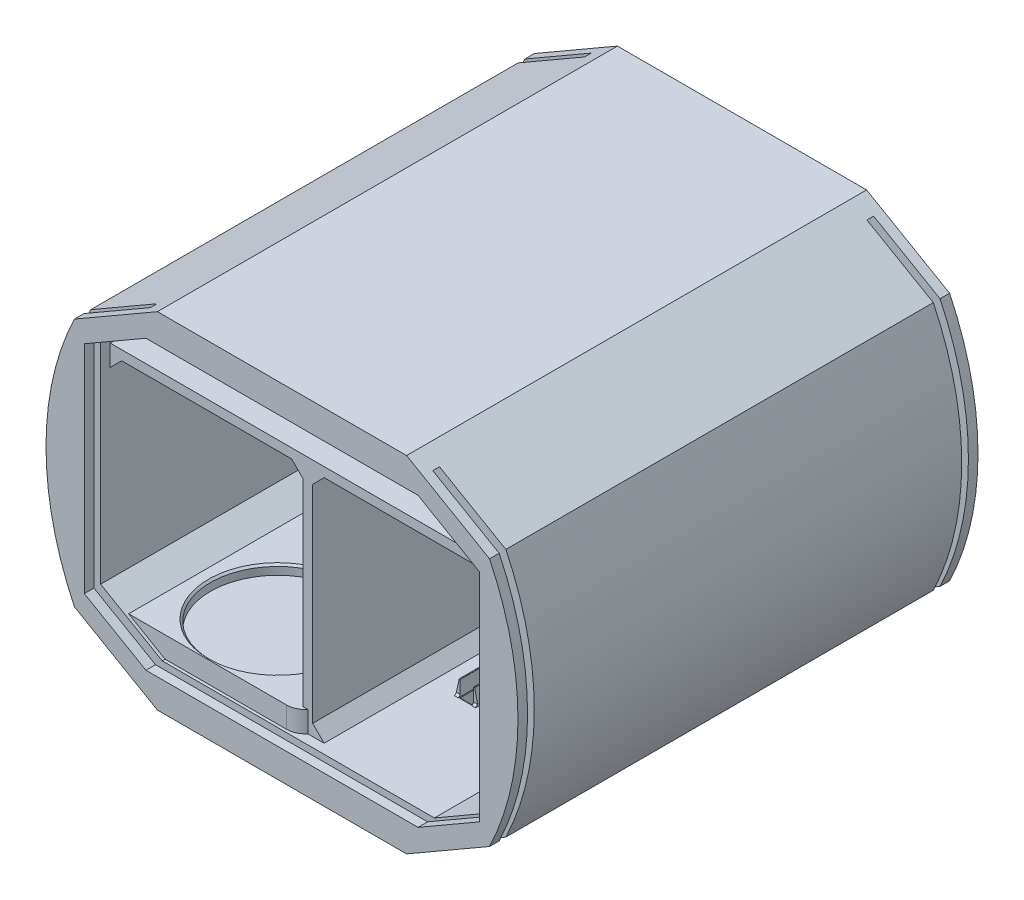
SolidWorks part; units mm, degrees
ref_plane "Front Plane" through (0, 0, 0) normal (0, 0, 1) x (1, 0, 0)
ref_plane "Top Plane" through (0, 0, 0) normal (0, 1, 0) x (1, 0, 0)
ref_plane "Right Plane" through (0, 0, 0) normal (1, 0, 0) x (0, 0, -1)
sketch "Sketch1" plane through (0, 0, 0) normal (0, 0, 1) x (1, 0, 0)
  line L0 (-65, 90) -> (-108.3013, 65)
  line L1 (-65, -90) -> (65, -90)
  line L3 (-65, 90) -> (65, 90)
  line L5 (-65, -90) -> (65, 90) construction
  line L6 (-65, 90) -> (65, -90) construction
  line L7 (-65, -90) -> (-108.3013, -65)
  line L8 (65, 90) -> (108.3013, 65)
  line L9 (65, -90) -> (108.3013, -65)
  arc A1 (-108.3013, 65) -> (-108.3013, -65) centre (26.8838, 0) ccw
  arc A4 (108.3013, 65) -> (108.3013, -65) centre (-26.8838, 0) cw
  point P0 (0, 0)
  point P7 (0, -90)
  dimension "D13" = 150
  dimension "D14" = 150
  dimension "D1" = 180
  dimension "D2" = 130
  dimension "D3" = 130
  dimension "D4" = 0
  dimension "D5" = 50
  dimension "D6" = 150
  dimension "D7" = 50
  dimension "D8" = 150
  dimension "D9" = 50
  dimension "D10" = 150
  dimension "D11" = 50
  dimension "D12" = 150
extrude "Boss-Extrude1" add sketch "Sketch1" along normal blind 240
sketch "Sketch2" plane through (0, 0, 240) normal (0, 0, 1) x (1, 0, 0)
  line L0 (-70.9808, 75) -> (70.9808, 75)
  line L1 (70.9808, 75) -> (103.1162, 56.4466)
  line L3 (65, 90) -> (-65, 90) construction
  line L4 (-70.9808, -75) -> (70.9808, -75)
  line L5 (70.9808, -75) -> (103.1162, -56.4466)
  line L6 (-65, -90) -> (65, -90) construction
  line L7 (108.3013, 65) -> (65, 90) construction
  line L8 (65, -90) -> (108.3013, -65) construction
  line L9 (-70.9808, 75) -> (-103.1162, 56.4466)
  line L10 (-70.9808, -75) -> (-103.1162, -56.4466)
  line L13 (-65, 90) -> (-108.3013, 65) construction
  line L15 (-108.3013, -65) -> (-65, -90) construction
  line L16 (-103.1162, 56.4466) -> (-103.1162, -56.4466)
  line L17 (103.1162, 56.4466) -> (103.1162, -56.4466)
  arc A0 (-108.3013, 65) -> (-108.3013, -65) centre (26.8838, 0) ccw construction
  arc A1 (108.3013, -65) -> (108.3013, 65) centre (-26.8838, 0) ccw construction
  point P24 (-123.1162, 0)
  point P28 (123.1162, 0)
  dimension "D1" = 15
  dimension "D2" = 10
  dimension "D3" = 20
  dimension "D4" = 15
  dimension "D5" = 20
  dimension "D7" = 10
  dimension "D8" = 10
  dimension "D10" = 10
sketch "Sketch3" plane through (0, 0, 0) normal (1, 0, 0) x (0, 0, -1)
  line L0 (-240, 90) -> (0, 90) construction
  line L1 (-235, 85) -> (-231.5, 85)
  line L2 (-235, 85) -> (-235, -85)
  line L3 (-235, -85) -> (-231.5, -85)
  line L4 (-231.5, 85) -> (-231.5, -85)
  line L5 (-240, -90) -> (0, -90) construction
  line L6 (-240, 65) -> (-240, -65) construction
  line L8 (-8.5, 85) -> (-5, 85)
  line L9 (-8.5, 85) -> (-8.5, -85)
  line L10 (-8.5, -85) -> (-5, -85)
  line L11 (-5, 85) -> (-5, -85)
  line L12 (0, -65) -> (0, 65) construction
  dimension "D1" = 5
  dimension "D2" = 5
  dimension "D3" = 5
  dimension "D4" = 3.5
  dimension "D5" = 5
  dimension "D6" = 5
  dimension "D7" = 5
  dimension "D8" = 3.5
extrude "Cut-Extrude4" cut sketch "Sketch2" against normal through all both and the other way through all
extrude "Cut-Extrude5" cut sketch "Sketch3" against normal through all both and the other way through all
sketch "Sketch7" plane through (0, 0, 0) normal (1, 0, 0) x (0, 0, -1)
  line L0 (-231.5, 65) -> (-231.5, -65) construction
  line L1 (-226.5, 45) -> (-13.5, 45)
  line L2 (-226.5, 45) -> (-226.5, 50)
  line L3 (-226.5, 50) -> (-13.5, 50)
  line L4 (-13.5, 45) -> (-13.5, 50)
  line L5 (-226.5, 45) -> (-13.5, 50) construction
  line L6 (-226.5, 50) -> (-13.5, 45) construction
  line L7 (-8.5, -65) -> (-8.5, 65) construction
  line L8 (-8.5, 75) -> (-231.5, 75) construction
  point P0 (-120, 47.5)
  dimension "D1" = 5
  dimension "D2" = 5
  dimension "D3" = 5
  dimension "D4" = 25
extrude "Boss-Extrude4" add sketch "Sketch7" along normal up to surface and the other way up to surface up to face at (103.1162, 0, 120) other way up to face at (-103.1162, 0, 120)
chamfer "Chamfer7" distance 6 angle 45 2 edges at (103.1162, 45, 120) (-103.1162, 45, 120)
sketch "Sketch8" plane through (0, -75, 0) normal (0, 1, 0) x (1, 0, 0)
  line L0 (-73.6603, -8.5) -> (-108.3013, -8.5) construction
  line L1 (-2.5, -226.5) -> (2.5, -226.5)
  line L2 (-2.5, -226.5) -> (-2.5, -13.5)
  line L3 (-2.5, -13.5) -> (2.5, -13.5)
  line L4 (2.5, -226.5) -> (2.5, -13.5)
  line L5 (-2.5, -226.5) -> (2.5, -13.5) construction
  line L6 (-2.5, -13.5) -> (2.5, -226.5) construction
  line L7 (-108.3013, -231.5) -> (-73.6603, -231.5) construction
  point P0 (0, -120)
  dimension "D1" = 5
  dimension "D2" = 5
  dimension "D3" = 5
extrude "Boss-Extrude5" add sketch "Sketch8" along normal up to surface (120 mm away) up to face at (0, 45, 120)
chamfer "Chamfer8" distance 6 angle 45 4 edges at (-2.5, 45, 120) (2.5, 45, 120) (2.5, -75, 120) (-2.5, -75, 120)
sketch "Sketch10" plane through (0, 0, 0) normal (1, 0, 0) x (0, 0, -1)
  line L0 (-240, -90) -> (0, -90) construction
  line L1 (-132.5, -75) -> (-107.5, -75)
  line L2 (-132.5, -75) -> (-132.5, -69)
  line L3 (-132.5, -69) -> (-107.5, -69)
  line L4 (-107.5, -75) -> (-107.5, -69)
  line L5 (-132.5, -75) -> (-107.5, -69) construction
  line L6 (-132.5, -69) -> (-107.5, -75) construction
  line L7 (-13.5, -75) -> (-226.5, -75) construction
  line L8 (-226.5, -69) -> (-13.5, -69) construction
  point P0 (-120, -72)
  point P7 (-120, -90)
  point P8 (-120, -75)
  dimension "D1" = 0
  dimension "D2" = 0
  dimension "D3" = 0
  dimension "D4" = 25
extrude "Cut-Extrude6" cut sketch "Sketch10" against normal blind 176 and the other way blind 23
sketch "Sketch12" plane through (0, 0, 0) normal (1, 0, 0) x (0, 0, -1)
  line L5 (-10, -64) -> (-230, -64)
  line L6 (-230, -64) -> (-230, -75)
  line L7 (-230, -75) -> (-132.5, -75)
  line L8 (-132.5, -75) -> (-132.5, -69)
  line L9 (-132.5, -69) -> (-107.5, -69)
  line L10 (-107.5, -69) -> (-107.5, -75)
  line L11 (-107.5, -75) -> (-10, -75)
  line L13 (-231.5, 56.4466) -> (-231.5, -56.4466) construction
  line L15 (-8.5, -75) -> (-107.5, -75) construction
  line L16 (-240, -90) -> (0, -90) construction
  line L17 (-10, -75) -> (-10, -64)
  line L18 (-8.5, -85) -> (-8.5, -65) construction
  point P16 (-120, -69)
  point P19 (-120, -90)
  dimension "D1" = 11
  dimension "D2" = 1.5
  dimension "D3" = 1.5
  dimension "D4" = 0
  dimension "D5" = 0
  dimension "D6" = 25
  dimension "D7" = 6
  dimension "D8" = 6
extrude "Boss-Extrude6" add sketch "Sketch12" against normal blind 90
fillet "Fillet1" radius 10 1 edges at (0, -69.5, 10)
fillet "Fillet2" radius 10 1 edges at (0, -69.5, 230)
sketch "Sketch13" plane through (0, 0, 0) normal (1, 0, 0) x (0, 0, -1)
  line L0 (-240, 90) -> (0, 90) construction
  line L1 (-8.5, 75) -> (-231.5, 75) construction
  circle A0 centre (-173.35, 62) radius 2.5
  circle A1 centre (-66.65, 62) radius 2.5
  circle A2 centre (-120, 62) radius 2.5
  point P6 (-120, 90)
  dimension "D1" = 53.35
  dimension "D5" = 5
  dimension "D6" = 5
  dimension "D7" = 5
  dimension "D2" = 53.35
  dimension "D3" = 13
  dimension "D4" = 13
extrude "Cut-Extrude7" cut sketch "Sketch13" against normal through all
sketch "Sketch14" plane through (0, 50, 0) normal (0, 1, 0) x (1, 0, 0)
  line L0 (103.1162, -226.5) -> (-103.1162, -226.5) construction
  line L1 (-2.5, -226.5) -> (-2.5, -13.5) construction
  circle A0 centre (-52.5, -119.8) radius 2.5
  dimension "D1" = 5
  dimension "D2" = 106.7
  dimension "D3" = 50
extrude "Cut-Extrude8" cut sketch "Sketch14" against normal blind 47
sketch "Sketch15" plane through (-103.1162, 0, 0) normal (1, 0, 0) x (0, 0, -1)
  line L0 (-231.5, 56.4466) -> (-231.5, -56.4466) construction
  line L1 (-8.5, -56.4466) -> (-8.5, 56.4466) construction
  line L2 (-13.5, 39) -> (-226.5, 39) construction
  circle A0 centre (-172.99, 24) radius 2.5
  circle A1 centre (-67.25, 24) radius 2.5
  dimension "D1" = 58.51
  dimension "D3" = 5
  dimension "D4" = 5
  dimension "D2" = 58.75
  dimension "D5" = 15
extrude "Cut-Extrude9" cut sketch "Sketch15" against normal blind 36
sketch "Sketch16" plane through (0, -75, 0) normal (0, 1, 0) x (1, 0, 0)
  line L0 (70.9808, -8.5) -> (70.9808, -231.5) construction
  line L1 (23.5, -170) -> (29.5, -170)
  line L2 (23.5, -170) -> (23.5, -70)
  line L3 (23.5, -70) -> (29.5, -70)
  line L4 (29.5, -170) -> (29.5, -70)
  line L5 (8.5, -13.5) -> (8.5, -107.5) construction
  line L7 (39.5, -162.5) -> (59.5, -162.5)
  line L8 (39.5, -162.5) -> (39.5, -77.5)
  line L9 (39.5, -77.5) -> (59.5, -77.5)
  line L10 (59.5, -162.5) -> (59.5, -77.5)
  point P4 (23.5, -120)
  point P7 (70.9808, -120)
  point P14 (59.5, -120)
  dimension "D1" = 6
  dimension "D2" = 100
  dimension "D3" = 0
  dimension "D4" = 15
  dimension "D5" = 20
  dimension "D6" = 85
  dimension "D7" = 0
  dimension "D8" = 10
extrude "Cut-Extrude10" cut sketch "Sketch16" against normal blind 8
sketch "Sketch20" plane through (0, -75, 0) normal (0, 1, 0) x (1, 0, 0)
  line L0 (59.5, -77.5) -> (39.5, -77.5) construction
  line L1 (23, -70) -> (21, -70)
  line L2 (23, -70) -> (23, -170)
  line L3 (23, -170) -> (21, -170)
  line L4 (21, -70) -> (21, -170)
  line L5 (30, -70) -> (32, -70)
  line L6 (30, -70) -> (30, -170)
  line L7 (30, -170) -> (32, -170)
  line L8 (32, -70) -> (32, -170)
  line L9 (37.5, -77.5) -> (39, -77.5)
  line L10 (37.5, -77.5) -> (37.5, -162.5)
  line L11 (37.5, -162.5) -> (39, -162.5)
  line L12 (39, -77.5) -> (39, -162.5)
  line L13 (61.5, -162.5) -> (60, -162.5)
  line L14 (61.5, -162.5) -> (61.5, -77.5)
  line L15 (61.5, -77.5) -> (60, -77.5)
  line L16 (60, -162.5) -> (60, -77.5)
  line L17 (39.5, -162.5) -> (59.5, -162.5) construction
  line L18 (29.5, -70) -> (23.5, -70) construction
  line L19 (23.5, -170) -> (29.5, -170) construction
  line L20 (29.5, -170) -> (29.5, -70) construction
  line L21 (23.5, -70) -> (23.5, -170) construction
  line L22 (39.5, -77.5) -> (39.5, -162.5) construction
  line L23 (59.5, -162.5) -> (59.5, -77.5) construction
  dimension "D1" = 1.5
  dimension "D2" = 1.5
  dimension "D3" = 2
  dimension "D4" = 2
  dimension "D5" = 0.5
  dimension "D6" = 0.5
  dimension "D7" = 0.5
  dimension "D8" = 0.5
extrude "Boss-Extrude7" add sketch "Sketch20" along normal blind 8
sketch "Sketch21" plane through (0, 0, 170) normal (0, 0, 1) x (1, 0, 0)
  line L0 (22.5, -67) -> (21, -73.7542)
  line L1 (21, -67) -> (21, -75) construction
  line L2 (21, -73.7542) -> (21, -67)
  line L3 (21, -67) -> (22.5, -67)
  line L4 (30.5, -67) -> (32, -67)
  line L5 (32, -67) -> (32, -73.7542)
  line L6 (32, -67) -> (32, -75) construction
  line L7 (32, -73.7542) -> (30.5, -67)
  line L8 (38.5, -67) -> (37.5, -73.7542)
  line L9 (37.5, -67) -> (37.5, -75) construction
  line L10 (37.5, -73.7542) -> (37.5, -67)
  line L11 (37.5, -67) -> (38.5, -67)
  line L12 (60.5, -67) -> (61.5, -73.7542)
  line L13 (61.5, -67) -> (61.5, -75) construction
  line L14 (61.5, -73.7542) -> (61.5, -67)
  line L15 (61.5, -67) -> (60.5, -67)
  line L16 (21, -67) -> (23, -67) construction
  line L17 (30, -67) -> (32, -67) construction
  line L18 (37.5, -67) -> (39, -67) construction
  line L19 (60, -67) -> (61.5, -67) construction
  dimension "D1" = 1.5
  dimension "D2" = 1.5
  dimension "D3" = 1
  dimension "D4" = 1
extrude "Cut-Extrude11" cut sketch "Sketch21" against normal up to next
fillet "Fillet4" radius 0.25 16 edges at (60.25, -67, 77.5) (38.75, -67, 77.5) (60.25, -67, 162.5) (38.75, -67, 162.5) (38.5, -67, 120) (39, -67, 120) (60, -67, 120) (60.5, -67, 120) (22.75, -67, 170) (22.5, -67, 120) (23, -67, 120) (22.75, -67, 70) (30.25, -67, 70) (30.25, -67, 170) (30.5, -67, 120) (30, -67, 120)
fillet "Fillet5" radius 1 4 edges at (26.5, -75, 170) (49.5, -75, 162.5) (26.5, -75, 70) (49.5, -75, 77.5)
sketch "Sketch22" plane through (61.5, 0, 0) normal (1, 0, 0) x (0, 0, -1)
  line L0 (-162.5, -75) -> (-77.5, -75) construction
  line L1 (-130, -75) -> (-110, -75)
  line L2 (-130, -75) -> (-130, -65)
  line L3 (-130, -65) -> (-110, -65)
  line L4 (-110, -75) -> (-110, -65)
  point P6 (-120, -75)
  point P7 (-120, -75)
  dimension "D1" = 20
  dimension "D2" = 10
extrude "Cut-Extrude12" cut sketch "Sketch22" against normal blind 43
chamfer "Chamfer9" distance 1 angle 45 16 edges at (60.75, -75, 77.5) (38.25, -75, 77.5) (31, -75, 70) (22, -75, 70) (22, -75, 110) (22, -75, 170) (31, -75, 170) (38.25, -75, 162.5) (60.75, -75, 162.5) (60.75, -75, 110) (31, -75, 110) (38.25, -75, 110) (22, -75, 130) (31, -75, 130) (38.25, -75, 130) (60.75, -75, 130)
sketch "Sketch24" plane through (0, 50, 0) normal (0, 1, 0) x (1, 0, 0)
  line L0 (-17.9178, -104) -> (17.9178, -104)
  line L1 (103.1162, -13.5) -> (103.1162, -226.5) construction
  line L5 (-32.9693, -110.0691) -> (-29.9693, -110.0691)
  line L6 (-17.9178, -101.5752) -> (17.9178, -101.5752)
  line L7 (29.9693, -110.0691) -> (32.9693, -110.0691)
  arc A0 (-17.9178, -104) -> (-29.9693, -110.0691) centre (-17.9178, -119) ccw
  arc A1 (17.9178, -104) -> (29.9693, -110.0691) centre (17.9178, -119) cw
  arc A3 (-32.9693, -110.0691) -> (-17.9178, -101.5752) centre (-19.4178, -116.5) cw
  arc A4 (32.9693, -110.0691) -> (17.9178, -101.5752) centre (19.4178, -116.5) ccw
  point P3 (0, -104)
  point P6 (103.1162, -120)
  dimension "D3" = 15
  dimension "D4" = 15
  dimension "D5" = 1.5
  dimension "D7" = 15
  dimension "D8" = 15
  dimension "D11" = 3
  dimension "D12" = 3
  dimension "D1" = 0
  dimension "D2" = 16
  dimension "D6" = 2.5
  dimension "D9" = 1.5
  dimension "D10" = 2.5
extrude "Boss-Extrude8" add sketch "Sketch24" along normal blind 8
fillet "Fillet6" radius 1 4 edges at (32.9693, 54, 110.0691) (29.9693, 54, 110.0691) (-32.9693, 54, 110.0691) (-29.9693, 54, 110.0691)
fillet "Fillet7" radius 1 12 edges at (-26.0172, 58, 103.0297) (-32.1578, 58, 109.5535) (-30.8728, 58, 110.0691) (-30.0273, 58, 109.9693) (-24.4502, 58, 105.4972) (26.0172, 58, 103.0297) (32.1578, 58, 109.5535) (30.8728, 58, 110.0691) (30.0273, 58, 109.9693) (24.4502, 58, 105.4972) (0, 58, 101.5752) (0, 58, 104)
sketch "Sketch25" plane through (0, -64, 0) normal (0, 1, 0) x (1, 0, 0)
  line L0 (-90, -10) -> (-7.5993, -10) construction
  line L1 (-2.5, -13.5) -> (-2.5, -226.5) construction
  line L3 (-90, -230) -> (-7.5993, -230) construction
  circle A0 centre (-48.7997, -46.5) radius 35
  circle A1 centre (-48.7997, -120) radius 35
  circle A2 centre (-48.7997, -193.5) radius 35
  point P9 (-48.7997, -10)
  point P13 (-2.5, -120)
  dimension "D1" = 70
  dimension "D2" = 70
  dimension "D3" = 70
  dimension "D4" = 36.5
  dimension "D5" = 36.5
extrude "Cut-Extrude13" cut sketch "Sketch25" against normal blind 5
sketch "Sketch26" plane through (0, 50, 0) normal (0, 1, 0) x (1, 0, 0)
  line L0 (70.9808, -8.5) -> (70.9808, -231.5) construction
  line L1 (73.9808, -155) -> (98.9808, -155)
  line L2 (73.9808, -155) -> (73.9808, -85)
  line L3 (73.9808, -85) -> (98.9808, -85)
  line L4 (98.9808, -155) -> (98.9808, -85)
  line L5 (73.9808, -155) -> (98.9808, -85) construction
  line L6 (73.9808, -85) -> (98.9808, -155) construction
  line L7 (108.3013, -231.5) -> (108.3013, -8.5) construction
  point P0 (86.4808, -120)
  point P9 (108.3013, -120)
  dimension "D1" = 70
  dimension "D2" = 25
  dimension "D3" = 3
  dimension "D4" = 0
extrude "Cut-Extrude14" cut sketch "Sketch26" against normal blind 12.5 from offset 105 offset against normal yes
sketch "Sketch27" plane through (0, -67.5, 0) normal (0, 1, 0) x (1, 0, 0)
  line L0 (83.9711, -155) -> (98.9808, -155) construction
  line L1 (83.9711, -85) -> (73.9711, -85)
  line L2 (83.9711, -85) -> (83.9711, -155)
  line L3 (83.9711, -155) -> (73.9711, -155)
  line L4 (73.9711, -85) -> (73.9711, -155)
  dimension "D1" = 10
extrude "Boss-Extrude9" add sketch "Sketch27" against normal blind 9
fillet "Fillet8" radius 1 5 edges at (78.9711, -67.5, 155) (73.9711, -70.3868, 155) (73.9711, -67.5, 120) (78.9711, -67.5, 85) (73.9711, -70.3868, 85)
sketch "Sketch28" plane through (0, 0, 155) normal (0, 0, 1) x (1, 0, 0)
  line L0 (73.9711, -73.2735) -> (83.9711, -67.5)
  line L2 (73.9711, -73.2735) -> (73.9711, -67.5)
  line L3 (73.9711, -67.5) -> (83.9711, -67.5)
extrude "Cut-Extrude15" cut sketch "Sketch28" against normal blind 10 from offset 30 offset against normal yes
fillet "Fillet9" radius 1 6 edges at (79.4711, -67.5, 125) (74.264, -67.7929, 125) (79.4711, -67.5, 115) (74.264, -67.7929, 115) (73.9711, -70.8868, 125) (73.9711, -70.8868, 115)
fillet "Fillet10" radius 2 3 edges at (91.476, -63.1671, 155) (98.9808, -58.8342, 120) (91.476, -63.1671, 85)
chamfer "Chamfer10" distance 1 angle 45 3 edges at (-48.7997, -64, 228.5) (-48.7997, -64, 81.5) (-48.7997, -64, 155)
